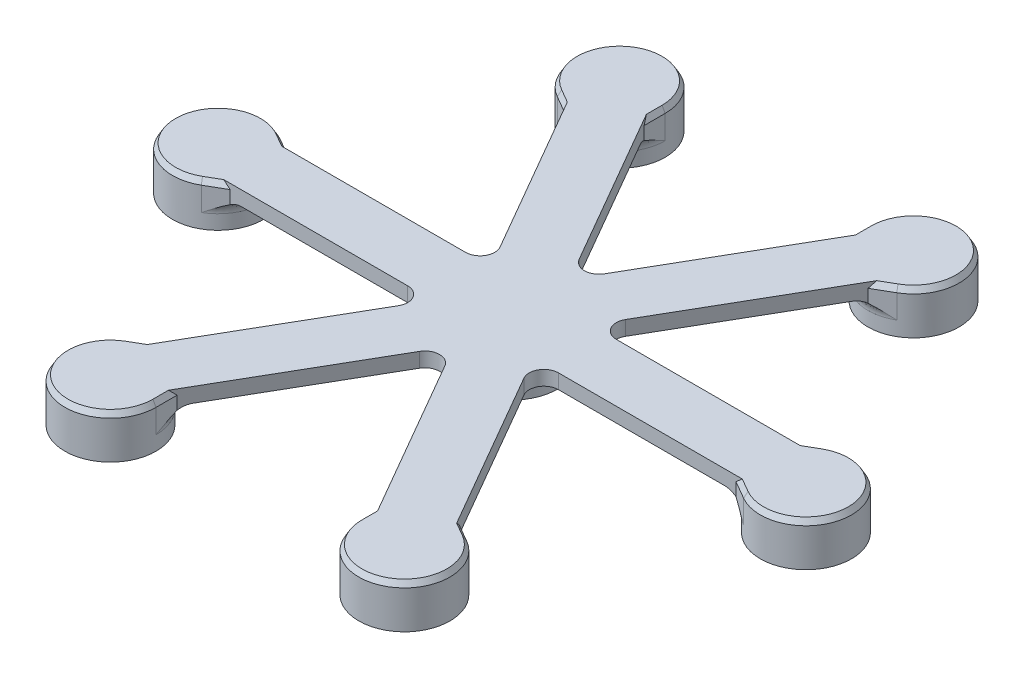
SolidWorks part; units mm, degrees
note: The reader was unsure of these and kept them because the rebuilt part matched: shared geometry of "Sketch1<4>".
ref_plane "Front Plane" through (0, 0, 0) normal (0, 0, 1) x (1, 0, 0)
ref_plane "Top Plane" through (0, 0, 0) normal (0, 1, 0) x (1, 0, 0)
ref_plane "Right Plane" through (0, 0, 0) normal (1, 0, 0) x (0, 0, -1)
sketch "Sketch1" plane through (0, 0, 0) normal (0, 1, 0) x (1, 0, 0)
  line L0 (-23.275, 29.4882) -> (-20.7744, 28.0445)
  line L1 (40.3, 0) -> (20.15, 34.9008) construction
  line L2 (20.15, 34.9008) -> (-20.15, 34.9008) construction
  line L3 (-20.15, 34.9008) -> (-40.3, 0) construction
  line L4 (-40.3, 0) -> (-20.15, -34.9008) construction
  line L5 (-20.15, -34.9008) -> (20.15, -34.9008) construction
  line L6 (20.15, -34.9008) -> (40.3, 0) construction
  line L7 (-37.175, 5.4127) -> (-34.6744, 3.9689)
  line L8 (-34.6744, 3.9689) -> (-20.7744, 28.0445) construction
  line L9 (-34.6744, 3.9689) -> (-10.3385, 3.9689)
  line L10 (13.9, 34.9008) -> (13.9, 32.0134)
  line L11 (-8.6065, 6.9689) -> (-20.7744, 28.0445)
  line L12 (-30.225, 17.4504) -> (0, 0) construction
  line L13 (-13.9, 34.9008) -> (-13.9, 32.0134)
  line L14 (-13.9, 32.0134) -> (-1.7321, 10.9379)
  line L15 (1.7321, 10.9379) -> (13.9, 32.0134)
  line L16 (37.175, 5.4127) -> (34.6744, 3.9689)
  line L17 (23.275, 29.4882) -> (20.7744, 28.0445)
  line L18 (20.7744, 28.0445) -> (8.6065, 6.9689)
  line L19 (10.3385, 3.9689) -> (34.6744, 3.9689)
  line L20 (23.275, -29.4882) -> (20.7744, -28.0445)
  line L21 (37.175, -5.4127) -> (34.6744, -3.9689)
  line L22 (34.6744, -3.9689) -> (10.3385, -3.9689)
  line L23 (8.6065, -6.9689) -> (20.7744, -28.0445)
  line L24 (-13.9, -34.9008) -> (-13.9, -32.0134)
  line L25 (13.9, -34.9008) -> (13.9, -32.0134)
  line L26 (13.9, -32.0134) -> (1.7321, -10.9379)
  line L27 (-1.7321, -10.9379) -> (-13.9, -32.0134)
  line L28 (-37.175, -5.4127) -> (-34.6744, -3.9689)
  line L29 (-23.275, -29.4882) -> (-20.7744, -28.0445)
  line L30 (-20.7744, -28.0445) -> (-8.6065, -6.9689)
  line L31 (-10.3385, -3.9689) -> (-34.6744, -3.9689)
  circle A0 centre (0, 0) radius 4
  circle A1 centre (0, 0) radius 34.9008 construction
  circle A3 centre (-20.15, 34.9008) radius 4
  arc A8 (-13.9, 34.9008) -> (-23.275, 29.4882) centre (-20.15, 34.9008) ccw
  arc A9 (-10.3385, 3.9689) -> (-8.6065, 6.9689) centre (-10.3385, 5.9689) ccw
  arc A10 (23.275, 29.4882) -> (13.9, 34.9008) centre (20.15, 34.9008) ccw
  arc A11 (-1.7321, 10.9379) -> (1.7321, 10.9379) centre (0, 11.9379) ccw
  arc A12 (37.175, -5.4127) -> (37.175, 5.4127) centre (40.3, 0) ccw
  arc A13 (8.6065, 6.9689) -> (10.3385, 3.9689) centre (10.3385, 5.9689) ccw
  arc A14 (13.9, -34.9008) -> (23.275, -29.4882) centre (20.15, -34.9008) ccw
  arc A15 (10.3385, -3.9689) -> (8.6065, -6.9689) centre (10.3385, -5.9689) ccw
  arc A16 (-23.275, -29.4882) -> (-13.9, -34.9008) centre (-20.15, -34.9008) ccw
  arc A17 (1.7321, -10.9379) -> (-1.7321, -10.9379) centre (0, -11.9379) ccw
  arc A18 (-37.175, 5.4127) -> (-37.175, -5.4127) centre (-40.3, 0) ccw
  arc A19 (-8.6065, -6.9689) -> (-10.3385, -3.9689) centre (-10.3385, -5.9689) ccw
  circle A20 centre (-40.3, 0) radius 4
  circle A21 centre (-20.15, -34.9008) radius 4
  circle A22 centre (20.15, -34.9008) radius 4
  circle A23 centre (40.3, 0) radius 4
  circle A24 centre (20.15, 34.9008) radius 4
  circle A25 centre (20.15, 34.9008) radius 6.25
  circle A26 centre (40.3, 0) radius 6.25
  circle A27 centre (20.15, -34.9008) radius 6.25
  circle A28 centre (-20.15, -34.9008) radius 6.25
  circle A29 centre (-40.3, 0) radius 6.25
  circle A30 centre (-20.15, 34.9008) radius 6.25
  circle A31 centre (0, 0) radius 6.25
  point P67 (0, 0)
  dimension "D1" = 8
  dimension "D3" = 2.25
  dimension "D4" = 2
  dimension "D2" = 40.3
  dimension "D5" = 6
extrude "Boss-Extrude2" add sketch "Sketch1" along normal blind 2 contours A20 | A18 A29 A20 | A30 L0 L11 A9 L9 L7 A29 L28 L31 A19 L30 L29 A28 L24 L27 A17 L26 L25 A27 L20 L23 A15 L22 L21 A26 L16 L19 A13 L18 L17 A25 L10 L15 A11 L14 L13 A0 | A3 | A8 A30 A3 | A24 | A10 A25 A24 | A23 | A12 A26 A23 | A14 A27 A22 | A22 | A16 A28 A21 | A21 | A0 | A31 A0
extrude "Boss-Extrude3" add sketch "Sketch1<4>" against normal blind 4.4 contours A12 A26 A23 | A31 A0 | A10 A25 A24 | A8 A30 A3 | A18 A29 A20 | A16 A28 A21 | A14 A27 A22
sketch "Sketch1<4>" plane through (0, 0, 0) normal (0, 1, 0) x (1, 0, 0) same geometry as "Sketch1"
sketch "Sketch2" plane through (0, 0, 0) normal (0, -1, 0) x (1, 0, 0)
  circle A0 centre (40.3, 0) radius 3.2
  circle A1 centre (40.3, 0) radius 4
  circle A2 centre (40.3, 0) radius 4 construction
  circle A3 centre (0, 0) radius 3.2
  circle A4 centre (0, 0) radius 4
  circle A5 centre (20.15, -34.9008) radius 3.2
  circle A6 centre (20.15, -34.9008) radius 4
  circle A7 centre (-20.15, -34.9008) radius 3.2
  circle A8 centre (-20.15, -34.9008) radius 4
  circle A9 centre (-40.3, 0) radius 3.2
  circle A10 centre (-40.3, 0) radius 4
  circle A11 centre (-20.15, 34.9008) radius 3.2
  circle A12 centre (-20.15, 34.9008) radius 4
  circle A13 centre (20.15, 34.9008) radius 3.2
  circle A14 centre (20.15, 34.9008) radius 4
  point P27 (0, 0)
  dimension "D1" = 0.8
  dimension "D2" = 6
extrude "Boss-Extrude4" add sketch "Sketch2" along normal blind 0.4
fillet "Fillet1" radius 2 19 edges at (34.05, 0, 0) (0, 0, 6.25) (17.025, 0, -29.4882) (-17.025, 0, -29.4882) (-34.05, 0, 0) (-17.025, 0, 29.4882) (17.025, 0, 29.4882) (-35.9247, 0, -4.6908) (-22.0247, 0, -28.7663) (-13.9, 0, -33.4571) (13.9, 0, -33.4571) (22.0247, 0, -28.7663) (35.9247, 0, -4.6908) (35.9247, 0, 4.6908) (22.0247, 0, 28.7663) (13.9, 0, 33.4571) (-13.9, 0, 33.4571) (-22.0247, 0, 28.7663) (-35.9247, 0, 4.6908)
chamfer "Chamfer2" distance 0.75 angle 30 32 edges at (20.15, -4.4, 41.1508) (20.15, -4.4, 38.9008) (-20.15, -4.4, 41.1508) (-20.15, -4.4, 38.9008) (0, -4.4, 6.25) (0, -4.4, 4) (-40.3, -4.4, 6.25) (-40.3, -4.4, 4) (-20.15, -4.4, -28.6508) (-20.15, -4.4, -30.9008) (40.3, -4.4, 6.25) (40.3, -4.4, 4) (20.15, -4.4, -28.6508) (20.15, -4.4, -30.9008) (22.0247, 2, -28.7663) (13.9, 2, -33.4571) (23.275, 2, -40.3135) (-13.9, 2, -33.4571) (-22.0247, 2, -28.7663) (-23.275, 2, -40.3135) (-35.9247, 2, -4.6908) (-35.9247, 2, 4.6908) (-46.55, 2, 0) (-22.0247, 2, 28.7663) (-13.9, 2, 33.4571) (-23.275, 2, 40.3135) (35.9247, 2, 4.6908) (35.9247, 2, -4.6908) (46.55, 2, 0) (13.9, 2, 33.4571) (22.0247, 2, 28.7663) (23.275, 2, 40.3135)
